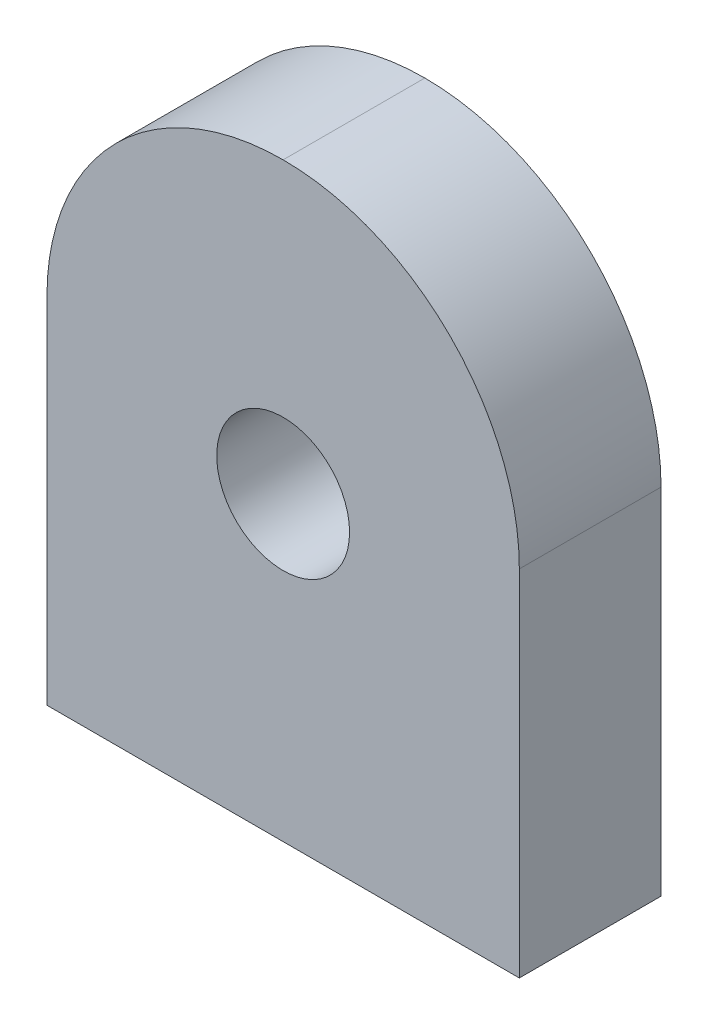
SolidWorks part; units mm, degrees
ref_plane "Front Plane" through (0, 0, 0) normal (0, 0, 1) x (1, 0, 0)
ref_plane "Top Plane" through (0, 0, 0) normal (0, 1, 0) x (1, 0, 0)
ref_plane "Right Plane" through (0, 0, 0) normal (1, 0, 0) x (0, 0, -1)
sketch "Sketch1" plane through (0, 0, 0) normal (0, 0, 1) x (1, 0, 0)
  line L1 (0, 0) -> (16, 0)
  line L2 (0, 0) -> (0, 20)
  line L3 (0, 20) -> (16, 20)
  line L4 (16, 0) -> (16, 20)
  dimension "D1" = 16
  dimension "D2" = 20
extrude "Boss-Extrude1" add sketch "Sketch1" along normal blind 4.8
sketch "Sketch2" plane through (0, 0, 4.8) normal (0, 0, 1) x (1, 0, 0)
  line L0 (8, 0) -> (8, 20) construction
  line L1 (0, 0) -> (16, 0) construction
  line L2 (16, 20) -> (0, 20) construction
  circle A0 centre (8, 10.2) radius 2.25
  dimension "D1" = 4.5
  dimension "D2" = 10.2
extrude "Cut-Extrude1" cut sketch "Sketch2" against normal through all
fillet "Fillet1" radius 8 2 edges at (16, 20, 2.4) (0, 20, 2.4)
